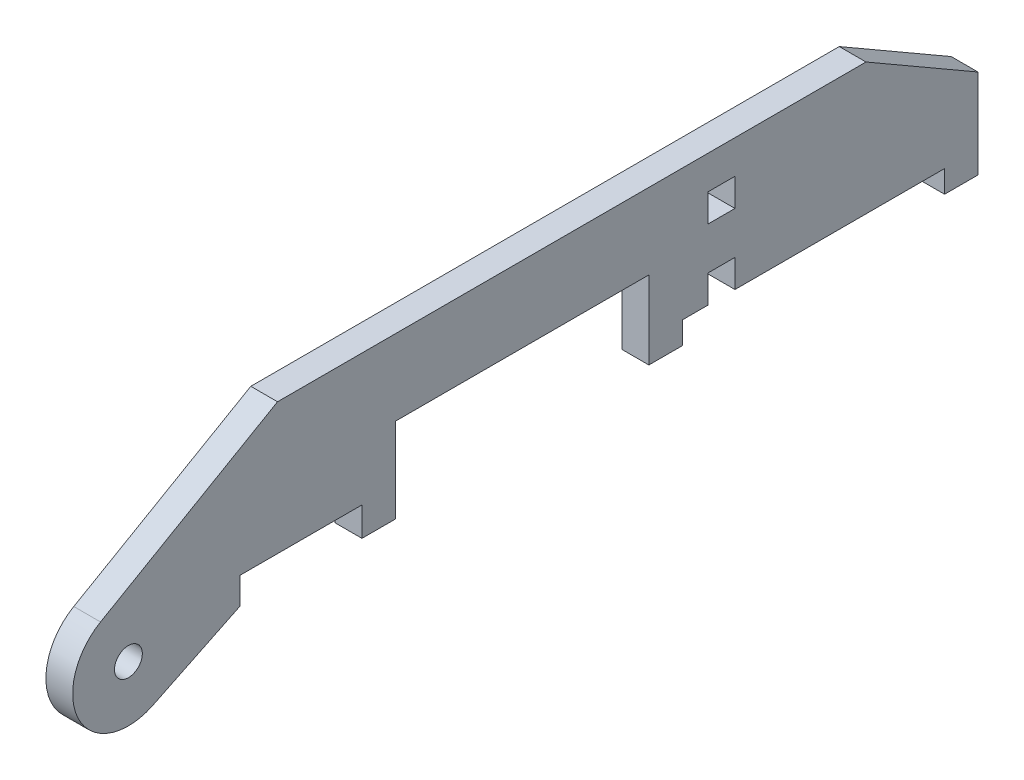
SolidWorks part; units mm, degrees
ref_plane "Front" through (0, 0, 0) normal (0, 0, 1) x (1, 0, 0)
ref_plane "Top" through (0, 0, 0) normal (0, 1, 0) x (1, 0, 0)
ref_plane "Right" through (0, 0, 0) normal (1, 0, 0) x (0, 0, -1)
ref_axis "side-side" through (80.9, 0, 0) along (-1, 0, 0)
ref_axis "up-down" through (0, 50, 0) along (0, -1, 0)
ref_axis "front-back" through (0, 0, -80.9) along (0, 0, 1)
sketch "Sketch1" plane through (0, 0, 0) normal (1, 0, 0) x (0, 0, -1)
  line L0 (-97.0573, 55.626) -> (-105.9473, 55.626) construction
  line L1 (-94.6424, 55.626) -> (-122.4573, 55.626)
  line L2 (-21.6519, 55.626) -> (-15.748, 55.626)
  line L3 (45.72, 50.546) -> (45.72, 70.866)
  line L4 (-87.0224, 49.022) -> (-87.0224, 68.326)
  line L5 (-87.0224, 68.326) -> (-29.2719, 68.326)
  line L6 (-29.2719, 50.546) -> (-29.2719, 68.326)
  line L7 (20.2034, 85.598) -> (-113.8762, 85.598)
  line L8 (45.72, 70.866) -> (20.2034, 85.598)
  line L9 (-122.4573, 55.626) -> (-122.4573, 49.53)
  line L10 (-97.0573, 49.53) -> (-105.9473, 49.53) construction
  line L11 (-122.4573, 49.53) -> (-142.3098, 39.89)
  line L12 (-132.6173, 55.626) -> (-132.6173, 49.53) construction
  line L13 (-154.2073, 62.3128) -> (-113.8762, 85.598)
  line L14 (38.1, 55.626) -> (27.94, 55.626) construction
  line L16 (45.72, 55.626) -> (45.72, 49.53) construction
  line L17 (-87.0224, 49.022) -> (-94.6424, 49.022)
  line L18 (-94.6424, 55.626) -> (-94.6424, 49.022)
  line L19 (-9.652, 55.626) -> (38.1, 55.626)
  line L21 (-29.2719, 50.546) -> (-21.6519, 50.546)
  line L22 (-21.6519, 55.626) -> (-21.6519, 50.546)
  line L23 (-15.748, 55.626) -> (-15.748, 61.976)
  line L24 (-15.748, 61.976) -> (-9.652, 61.976)
  line L25 (45.72, 50.546) -> (38.1, 50.546)
  line L26 (38.1, 55.626) -> (38.1, 50.546)
  line L27 (-9.652, 55.626) -> (-9.652, 61.976)
  line L28 (-9.652, 77.978) -> (-15.748, 77.978)
  line L29 (-9.652, 77.978) -> (-9.652, 71.628)
  line L30 (-9.652, 71.628) -> (-15.748, 71.628)
  line L31 (-15.748, 77.978) -> (-15.748, 71.628)
  arc A0 (-154.2073, 62.3128) -> (-142.3098, 39.89) centre (-147.8573, 51.3143) ccw
  circle A1 centre (-147.8573, 51.3143) radius 12.7 construction
  circle A2 centre (-147.8573, 51.3143) radius 3.175 construction
  circle A3 centre (-147.8573, 51.3143) radius 3.175
  dimension "D1" = 12.7
  dimension "D2" = 17.272
  dimension "D3" = 10.16
  dimension "D4" = 30
  dimension "D5" = 30
  dimension "D6" = 15.24
  dimension "D7" = 5.08
  dimension "D8" = 6.604
extrude "Boss-Extrude1" add sketch "Sketch1" along normal mid plane 6.096
